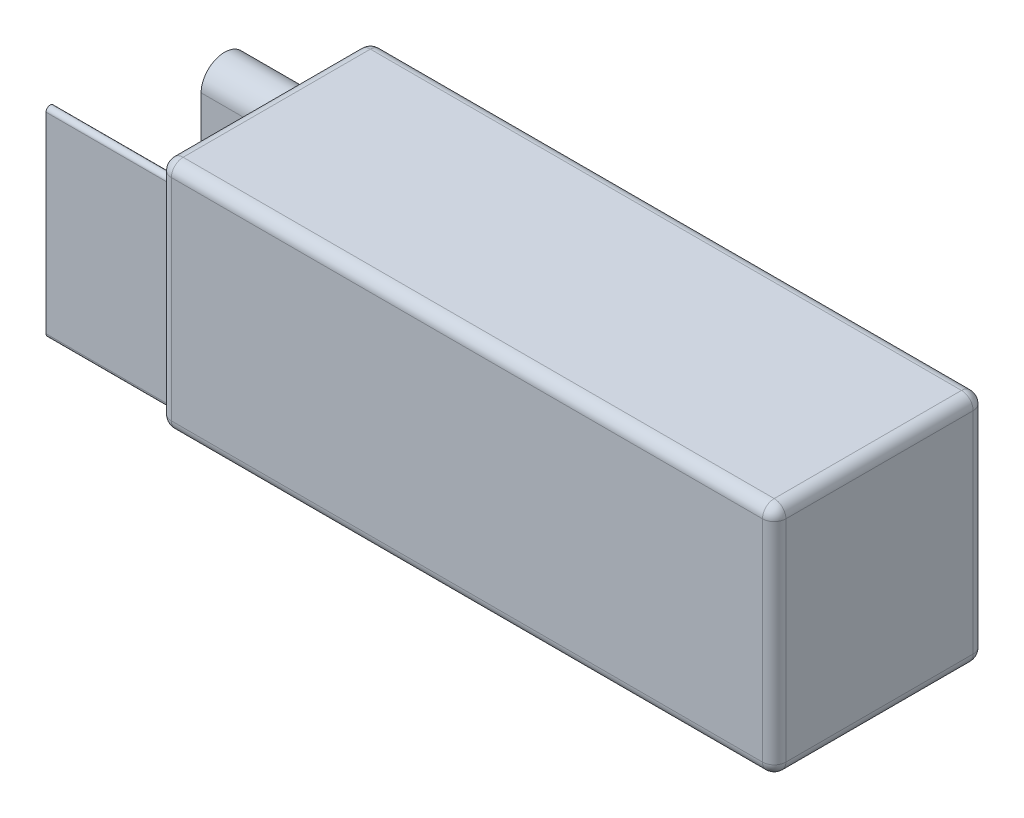
SolidWorks part; units mm, degrees
ref_plane "Front Plane" through (0, 0, 0) normal (0, 0, 1) x (1, 0, 0)
ref_plane "Top Plane" through (0, 0, 0) normal (0, 1, 0) x (1, 0, 0)
ref_plane "Right Plane" through (0, 0, 0) normal (1, 0, 0) x (0, 0, -1)
sketch "Sketch1" plane through (0, 0, 0) normal (0, 1, 0) x (1, 0, 0)
  line L1 (0, 0) -> (105, 0)
  line L2 (0, 0) -> (0, 36)
  line L3 (0, 36) -> (105, 36)
  line L4 (105, 0) -> (105, 36)
  dimension "D1" = 105
  dimension "D2" = 36
extrude "Boss-Extrude1" add sketch "Sketch1" along normal blind 40
sketch "Sketch2" plane through (0, 0, 0) normal (-1, 0, 0) x (0, 0, 1)
  line L0 (-31.0781, 14) -> (-31.0781, 26) construction
  line L1 (-35.0781, 14) -> (-35.0781, 26)
  line L2 (-27.0781, 14) -> (-27.0781, 26)
  line L3 (-1.2757, 36.3887) -> (-1.2757, 3.6113) construction
  line L4 (-0.5766, 36.3887) -> (-0.5766, 3.6113)
  line L5 (-1.9749, 36.3887) -> (-1.9749, 3.6113)
  line L6 (-31.0781, 20) -> (-1.2757, 20) construction
  line L7 (-36, 20) -> (-31.0781, 20) construction
  line L8 (-36, 40) -> (-36, 0) construction
  arc A0 (-35.0781, 14) -> (-27.0781, 14) centre (-31.0781, 14) ccw
  arc A1 (-27.0781, 26) -> (-35.0781, 26) centre (-31.0781, 26) ccw
  arc A2 (-0.5766, 36.3887) -> (-1.9749, 36.3887) centre (-1.2757, 36.3887) ccw
  arc A3 (-1.9749, 3.6113) -> (-0.5766, 3.6113) centre (-1.2757, 3.6113) ccw
  point P2 (-31.0781, 20)
  point P7 (-1.2757, 20)
  dimension "D1" = 12
  dimension "D2" = 8
extrude "Boss-Extrude2" add sketch "Sketch2" along normal blind 20
fillet "Fillet1" radius 2 12 edges at (105, 0, -18) (0, 0, -18) (105, 20, -36) (0, 20, -36) (52.5, 0, -36) (52.5, 40, -36) (105, 40, -18) (0, 40, -18) (0, 20, 0) (52.5, 40, 0) (105, 20, 0) (52.5, 0, 0)
